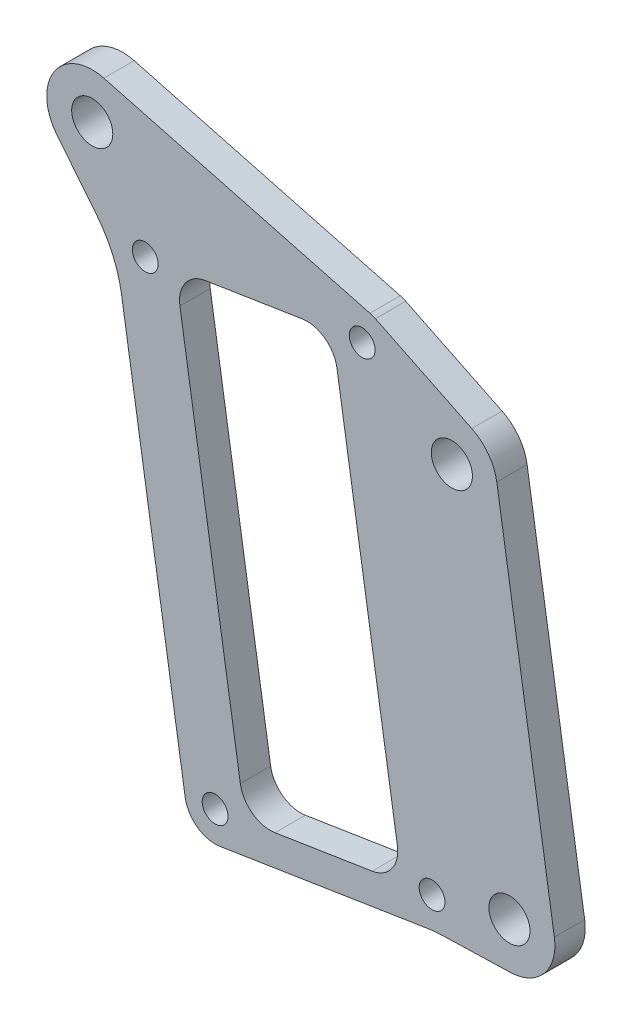
SolidWorks part; units mm, degrees
material "ABS PC"
ref_plane "Front Plane" through (0, 0, 0) normal (0, 0, 1) x (1, 0, 0)
ref_plane "Top Plane" through (0, 0, 0) normal (0, 1, 0) x (1, 0, 0)
ref_plane "Right Plane" through (0, 0, 0) normal (1, 0, 0) x (0, 0, -1)
sketch "Sketch1" plane through (0, 0, 0) normal (0, 0, 1) x (1, 0, 0)
  line L0 (-3.7107, -2.9853) -> (3.0775, -11.4229)
  line L1 (2.4151, -9.927) -> (9.7328, -56.3539)
  line L2 (1.2203, 4.6035) -> (29.0844, -2.7827)
  line L3 (29.661, -2.9972) -> (39.7487, -7.9099)
  line L4 (42.3679, -11.4501) -> (48.3988, -49.7127)
  line L5 (35.681, -55.4522) -> (43.8331, -55.2147)
  line L6 (13.3634, -58.9958) -> (36.0829, -55.4148)
  line L7 (5.5513, -9.4327) -> (35.5886, -52.2785) construction
  line L8 (20.57, -30.8556) -> (15.581, 0.7968) construction
  line L9 (32.4523, -52.7729) -> (25.1346, -6.346)
  line L10 (32.4523, -52.7729) -> (16.0054, -55.3652)
  line L11 (25.1346, -6.346) -> (8.6876, -8.9384)
  line L12 (16.0054, -55.3652) -> (8.6876, -8.9384)
  line L13 (32.4523, -52.7729) -> (8.6876, -8.9384) construction
  line L14 (25.1346, -6.346) -> (16.0054, -55.3652) construction
  circle A0 centre (37.6635, -12.1916) radius 4.7625
  circle A1 centre (43.6944, -50.4542) radius 4.7625
  circle A2 centre (37.6635, -12.1916) radius 2.15 construction
  circle A3 centre (43.6944, -50.4542) radius 2.15 construction
  circle A4 centre (0, 0) radius 4.7625
  circle A5 centre (0, 0) radius 2.15 construction
  circle A6 centre (35.5886, -52.2785) radius 3.175
  circle A7 centre (12.8691, -55.8595) radius 3.175
  circle A8 centre (5.5513, -9.4327) radius 3.175
  circle A9 centre (28.2709, -5.8517) radius 3.175
  circle A10 centre (12.8691, -55.8595) radius 1.6 construction
  circle A11 centre (35.5886, -52.2785) radius 1.6 construction
  circle A12 centre (28.2709, -5.8517) radius 1.6 construction
  circle A13 centre (5.5513, -9.4327) radius 1.6 construction
  point P40 (0, 0)
  point P49 (0, 0)
  point P52 (0, 0)
  dimension "D1" = 9.525
  dimension "D2" = 6.35
  dimension "D3" = 3.175
extrude "Boss-Extrude1" add sketch "Sketch1" along normal blind 3.175 contours A9 | A9 L2 A4 L0 L1 A8 L11 | A4 | A8 | A8 L0 L1 A7 L12 | A7 | A7 L6 L5 A6 L10 | A1 A6 | A6 L6 L5 A1 | A6 A1 | A1 A6 | A6 L5 L6 | A9 L9 A6 A1 L4 A0 L3 | A0 | A8 L1 L0 region at (12.3555, -3.404, 0) region at (0, 0, 0) region at (2.6276, -10.7276, 0) region at (9.2117, -32.6511, 0) region at (5.5513, -9.4327, 0) region at (12.8691, -55.8595, 0) region at (28.2709, -5.8517, 0) region at (24.4862, -55.7028, 0) region at (36.4567, -29.7633, 0) region at (35.5886, -52.2785, 0) region at (35.8827, -55.4412, 0) region at (37.6635, -12.1916, 0) region at (43.6944, -50.4542, 0)
fillet "Fillet1" radius 3.175 4 edges at (32.4523, -52.7729, 1.5875) (25.1346, -6.346, 1.5875) (16.0054, -55.3652, 1.5875) (8.6876, -8.9384, 1.5875)
fillet "Fillet2" radius 12.7 2 edges at (35.8832, -55.4463, 1.5875) (2.5469, -10.7633, 1.5875)
hole_wizard "#2 Clearance Hole1" positions "Sketch2" profile "Sketch3" hole size "#2" standard "ANSI Inch" end condition through all
sketch "Sketch2" plane through (0, 0, 3.175) normal (0, 0, 1) x (1, 0, 0)
  line L0 (5.5513, -9.4327) -> (35.5886, -52.2785) construction
  point P0 (5.5513, -9.4327)
  point P4 (28.2709, -5.8517)
  point P7 (35.5886, -52.2785)
  point P10 (12.8691, -55.8595)
sketch "Sketch3" plane through (5.5513, -9.4327, 3.175) normal (1, 0, 0) x (0, -1, 0)
  line L0 (0, 0) -> (0, 3.175)
  line L1 (0, 3.175) -> (1.3525, 3.175)
  line L2 (1.3525, 3.175) -> (1.3525, 0)
  line L5 (1.3525, 0) -> (0, 0)
  line L11 (0, -6.35) -> (0, 107.95) construction
  dimension "Thru Hole Dia." = 2.7051
  dimension "Thru Hole Depth" = 3.175
hole_wizard "#6 Clearance Hole1" positions "Sketch4" profile "Sketch5" hole size "#6" standard "ANSI Inch" end condition through all
sketch "Sketch4" plane through (0, 0, 3.175) normal (0, 0, 1) x (1, 0, 0)
  point P0 (0, 0)
  point P3 (37.6635, -12.1916)
  point P6 (43.6944, -50.4542)
sketch "Sketch5" plane through (0, 0, 3.175) normal (1, 0, 0) x (0, -1, 0)
  line L0 (0, 0) -> (0, 3.175)
  line L1 (0, 3.175) -> (2.1526, 3.175)
  line L2 (2.1526, 3.175) -> (2.1526, 0)
  line L5 (2.1526, 0) -> (0, 0)
  line L11 (0, -6.35) -> (0, 107.95) construction
  dimension "Thru Hole Dia." = 4.3053
  dimension "Thru Hole Depth" = 3.175
